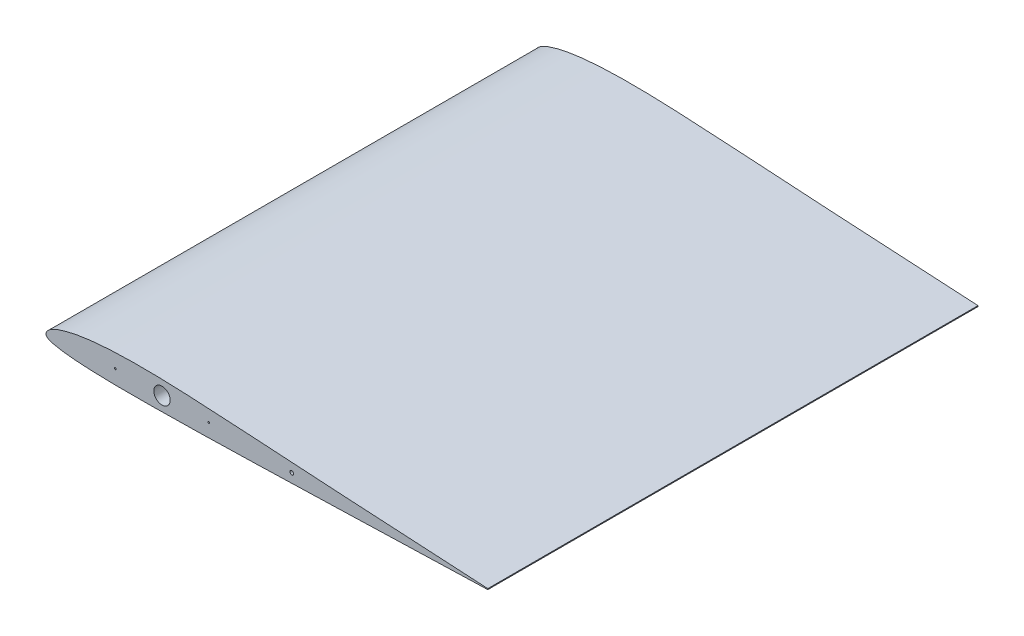
SolidWorks part; units mm, degrees
material "Polyurethane Foam Flexible"
ref_plane "Front Plane" through (0, 0, 0) normal (0, 0, 1) x (1, 0, 0)
ref_plane "Top Plane" through (0, 0, 0) normal (0, 1, 0) x (1, 0, 0)
ref_plane "Right Plane" through (0, 0, 0) normal (1, 0, 0) x (0, 0, -1)
curve "ht32-8-imported"
  spline degree 3 poles (203.2026, 0.2115, 0) (202.75, 0.2358, 0) (201.4822, 0.3036, 0) (199.2299, 0.4276, 0) (196.3046, 0.5865, 0) (192.9787, 0.7694, 0) (189.375, 0.9706, 0) (185.6129, 1.1785, 0) (181.7737, 1.3957, 0) (177.8996, 1.6147, 0) (174.01, 1.8354, 0) (170.1132, 2.0552, 0) (166.2133, 2.2775, 0) (162.3117, 2.4986, 0) (158.4107, 2.722, 0) (154.5106, 2.9441, 0) (150.6142, 3.1678, 0) (146.7204, 3.3936, 0) (142.8309, 3.617, 0) (138.944, 3.8454, 0) (135.0595, 4.0721, 0) (131.1775, 4.3012, 0) (127.2967, 4.5315, 0) (123.4189, 4.7649, 0) (119.5421, 5.0008, 0) (115.6675, 5.2398, 0) (111.7949, 5.4816, 0) (107.9236, 5.7247, 0) (104.0572, 5.9681, 0) (100.1894, 6.212, 0) (96.3188, 6.4543, 0) (92.4477, 6.6946, 0) (88.584, 6.9322, 0) (84.7415, 7.1637, 0) (80.9229, 7.3889, 0) (77.3978, 7.5906, 0) (74.5229, 7.7493, 0) (71.9946, 7.8843, 0) (69.1241, 8.0324, 0) (65.5083, 8.2076, 0) (61.4852, 8.3831, 0) (57.5218, 8.5328, 0) (53.6734, 8.652, 0) (49.9058, 8.739, 0) (46.181, 8.7912, 0) (42.491, 8.8047, 0) (38.8468, 8.7742, 0) (35.2596, 8.6962, 0) (31.7561, 8.5671, 0) (28.3661, 8.3856, 0) (25.1292, 8.152, 0) (22.0798, 7.8688, 0) (19.2587, 7.5428, 0) (16.7019, 7.1837, 0) (14.4336, 6.8058, 0) (12.4541, 6.4216, 0) (10.7471, 6.0418, 0) (9.283, 5.6741, 0) (8.0264, 5.3216, 0) (6.9394, 4.9844, 0) (5.9876, 4.6599, 0) (5.1429, 4.3427, 0) (4.3754, 4.0301, 0) (3.6577, 3.7081, 0) (2.9646, 3.3607, 0) (2.2868, 2.9708, 0) (1.6384, 2.5305, 0) (1.05, 2.0355, 0) (0.5511, 1.4823, 0) (0.1821, 0.8795, 0) (0.0202, 0.3651, 0) (-0.0065, -0.0193, 0) (0.0194, -0.3136, 0) (0.1268, -0.6144, 0) (0.297, -0.8546, 0) (0.4742, -1.036, 0) (0.6922, -1.2054, 0) (0.9846, -1.3848, 0) (1.3525, -1.5668, 0) (1.7794, -1.7448, 0) (2.2605, -1.9172, 0) (2.8067, -2.0876, 0) (3.4413, -2.2602, 0) (4.1881, -2.438, 0) (5.0669, -2.6215, 0) (6.0922, -2.8069, 0) (7.2766, -2.9931, 0) (8.6343, -3.178, 0) (10.1869, -3.3594, 0) (11.9608, -3.5369, 0) (13.9882, -3.7077, 0) (16.2949, -3.8689, 0) (18.8937, -4.0155, 0) (21.7662, -4.1437, 0) (24.8729, -4.2492, 0) (28.1584, -4.3297, 0) (31.5775, -4.3867, 0) (35.0914, -4.4207, 0) (38.6791, -4.4351, 0) (42.3216, -4.4311, 0) (46.0126, -4.4125, 0) (49.7579, -4.3795, 0) (53.5805, -4.3372, 0) (57.5149, -4.2842, 0) (61.5959, -4.2202, 0) (65.8841, -4.1445, 0) (69.584, -4.0721, 0) (72.8088, -4.005, 0) (75.5799, -3.9448, 0) (78.7708, -3.8727, 0) (82.2137, -3.7909, 0) (85.8123, -3.7021, 0) (89.4548, -3.6091, 0) (93.1502, -3.5116, 0) (96.8889, -3.4111, 0) (100.657, -3.3069, 0) (104.4397, -3.2018, 0) (108.2248, -3.0945, 0) (112.0082, -2.9863, 0) (115.791, -2.8766, 0) (119.5782, -2.7658, 0) (123.3765, -2.6523, 0) (127.1945, -2.5376, 0) (131.0416, -2.42, 0) (134.9198, -2.302, 0) (138.8194, -2.1823, 0) (142.7263, -2.0602, 0) (146.6334, -1.9373, 0) (150.5405, -1.8169, 0) (154.4476, -1.6935, 0) (158.3547, -1.5735, 0) (162.2615, -1.4515, 0) (166.1675, -1.3317, 0) (170.0718, -1.2089, 0) (173.9729, -1.0897, 0) (177.8669, -0.9678, 0) (181.7453, -0.8488, 0) (185.5889, -0.7312, 0) (189.3549, -0.6169, 0) (192.9626, -0.5096, 0) (196.292, -0.413, 0) (199.2203, -0.3248, 0) (201.4752, -0.2617, 0) (202.7443, -0.2247, 0) (203.1974, -0.2115, 0) knots 0 0 0 0 0.003316 0.009286 0.0165 0.024744 0.033651 0.0429 0.052304 0.061778 0.071282 0.080801 0.090326 0.099855 0.109385 0.118907 0.128429 0.137932 0.147436 0.156926 0.166412 0.175898 0.185369 0.194848 0.204314 0.213779 0.223243 0.232695 0.242152 0.25158 0.261042 0.270519 0.279949 0.289356 0.298677 0.307928 0.315183 0.319737 0.326448 0.336207 0.346216 0.355902 0.365219 0.374379 0.383467 0.392467 0.401369 0.410123 0.41871 0.427012 0.434953 0.442447 0.449411 0.455723 0.46133 0.466229 0.470471 0.47412 0.47727 0.480016 0.482444 0.484624 0.486615 0.488504 0.490376 0.492284 0.49422 0.496102 0.497896 0.499646 0.501237 0.501776 0.502457 0.503386 0.504071 0.504595 0.505236 0.506086 0.5071 0.508235 0.509467 0.510837 0.512419 0.514277 0.516452 0.518985 0.521897 0.525221 0.529007 0.53333 0.538261 0.543889 0.550243 0.557299 0.56492 0.57298 0.581338 0.589931 0.598683 0.607581 0.616575 0.625681 0.634977 0.644537 0.654462 0.664831 0.675908 0.681531 0.688425 0.696181 0.704877 0.713615 0.722511 0.731528 0.740655 0.749867 0.759101 0.768335 0.777565 0.786786 0.796016 0.805278 0.814581 0.823955 0.833431 0.842961 0.852492 0.862023 0.871554 0.881085 0.890615 0.900146 0.909675 0.9192 0.928718 0.938223 0.947696 0.9571 0.96635 0.975256 0.9835 0.990713 0.996685 1 1 1 1
sketch "Sketch3" plane through (0, 0, 0) normal (0, 0, 1) x (1, 0, 0)
  line L3 (203.2026, 0.2115) -> (203.1974, -0.2115)
  spline S0 degree 3 poles (356.7908, -2985.9067) (413.0686, 1.836) (306.2858, -5.4633) (199.2299, 0.4276) (196.3046, 0.5865) (192.9787, 0.7694) (189.375, 0.9706) (185.6129, 1.1785) (181.7737, 1.3957) (177.8996, 1.6147) (174.01, 1.8354) (170.1132, 2.0552) (166.2133, 2.2775) (162.3117, 2.4986) (158.4107, 2.722) (154.5106, 2.9441) (150.6142, 3.1678) (146.7204, 3.3936) (142.8309, 3.617) (138.944, 3.8454) (135.0595, 4.0721) (131.1775, 4.3012) (127.2967, 4.5315) (123.4189, 4.7649) (119.5421, 5.0008) (115.6675, 5.2398) (111.7949, 5.4816) (107.9236, 5.7247) (104.0572, 5.9681) (100.1894, 6.212) (96.3188, 6.4543) (92.4477, 6.6946) (88.584, 6.9322) (84.7415, 7.1637) (80.9229, 7.3889) (77.3978, 7.5906) (74.5229, 7.7493) (71.9946, 7.8843) (69.1241, 8.0324) (65.5083, 8.2076) (61.4852, 8.3831) (57.5218, 8.5328) (53.6734, 8.652) (49.9058, 8.739) (46.181, 8.7912) (42.491, 8.8047) (38.8468, 8.7742) (35.2596, 8.6962) (31.7561, 8.5671) (28.3661, 8.3856) (25.1292, 8.152) (22.0798, 7.8688) (19.2587, 7.5428) (16.7019, 7.1837) (14.4336, 6.8058) (12.4541, 6.4216) (10.7471, 6.0418) (9.283, 5.6741) (8.0264, 5.3216) (6.9394, 4.9844) (5.9876, 4.6599) (5.1429, 4.3427) (4.3754, 4.0301) (3.6577, 3.7081) (2.9646, 3.3607) (2.2868, 2.9708) (1.6384, 2.5305) (1.05, 2.0355) (0.5511, 1.4823) (0.1821, 0.8795) (0.0202, 0.3651) (-0.0065, -0.0193) (0.0194, -0.3136) (0.1268, -0.6144) (0.297, -0.8546) (0.4742, -1.036) (0.6922, -1.2054) (0.9846, -1.3848) (1.3525, -1.5668) (1.7794, -1.7448) (2.2605, -1.9172) (2.8067, -2.0876) (3.4413, -2.2602) (4.1881, -2.438) (5.0669, -2.6215) (6.0922, -2.8069) (7.2766, -2.9931) (8.6343, -3.178) (10.1869, -3.3594) (11.9608, -3.5369) (13.9882, -3.7077) (16.2949, -3.8689) (18.8937, -4.0155) (21.7662, -4.1437) (24.8729, -4.2492) (28.1584, -4.3297) (31.5775, -4.3867) (35.0914, -4.4207) (38.6791, -4.4351) (42.3216, -4.4311) (46.0126, -4.4125) (49.7579, -4.3795) (53.5805, -4.3372) (57.5149, -4.2842) (61.5959, -4.2202) (65.8841, -4.1445) (69.584, -4.0721) (72.8088, -4.005) (75.5799, -3.9448) (78.7708, -3.8727) (82.2137, -3.7909) (85.8123, -3.7021) (89.4548, -3.6091) (93.1502, -3.5116) (96.8889, -3.4111) (100.657, -3.3069) (104.4397, -3.2018) (108.2248, -3.0945) (112.0082, -2.9863) (115.791, -2.8766) (119.5782, -2.7658) (123.3765, -2.6523) (127.1945, -2.5376) (131.0416, -2.42) (134.9198, -2.302) (138.8194, -2.1823) (142.7263, -2.0602) (146.6334, -1.9373) (150.5405, -1.8169) (154.4476, -1.6935) (158.3547, -1.5735) (162.2615, -1.4515) (166.1675, -1.3317) (170.0718, -1.2089) (173.9729, -1.0897) (177.8669, -0.9678) (181.7453, -0.8488) (185.5889, -0.7312) (189.3549, -0.6169) (192.9626, -0.5096) (196.292, -0.413) (199.2203, -0.3248) (315.412, 2.9269) (430.2694, 18.2159) (630.7155, -2957.7378) knots -0.767748 -0.767748 -0.767748 -0.767748 0.003316 0.009286 0.0165 0.024744 0.033651 0.0429 0.052304 0.061778 0.071282 0.080801 0.090326 0.099855 0.109385 0.118907 0.128429 0.137932 0.147436 0.156926 0.166412 0.175898 0.185369 0.194848 0.204314 0.213779 0.223243 0.232695 0.242152 0.25158 0.261042 0.270519 0.279949 0.289356 0.298677 0.307928 0.315183 0.319737 0.326448 0.336207 0.346216 0.355902 0.365219 0.374379 0.383467 0.392467 0.401369 0.410123 0.41871 0.427012 0.434953 0.442447 0.449411 0.455723 0.46133 0.466229 0.470471 0.47412 0.47727 0.480016 0.482444 0.484624 0.486615 0.488504 0.490376 0.492284 0.49422 0.496102 0.497896 0.499646 0.501237 0.501776 0.502457 0.503386 0.504071 0.504595 0.505236 0.506086 0.5071 0.508235 0.509467 0.510837 0.512419 0.514277 0.516452 0.518985 0.521897 0.525221 0.529007 0.53333 0.538261 0.543889 0.550243 0.557299 0.56492 0.57298 0.581338 0.589931 0.598683 0.607581 0.616575 0.625681 0.634977 0.644537 0.654462 0.664831 0.675908 0.681531 0.688425 0.696181 0.704877 0.713615 0.722511 0.731528 0.740655 0.749867 0.759101 0.768335 0.777565 0.786786 0.796016 0.805278 0.814581 0.823955 0.833431 0.842961 0.852492 0.862023 0.871554 0.881085 0.890615 0.900146 0.909675 0.9192 0.928718 0.938223 0.947696 0.9571 0.96635 0.975256 0.9835 0.990713 0.996685 1.83372 1.83372 1.83372 1.83372 only from (203.2026, 0.2115) to (203.1974, -0.2115) construction
  spline S1 degree 3 poles (203.2026, 0.2115) (202.75, 0.2358) (201.4822, 0.3036) (199.2299, 0.4276) (196.3046, 0.5865) (192.9787, 0.7694) (189.375, 0.9706) (185.6129, 1.1785) (181.7737, 1.3957) (177.8996, 1.6147) (174.01, 1.8354) (170.1132, 2.0552) (166.2133, 2.2775) (162.3117, 2.4986) (158.4107, 2.722) (154.5106, 2.9441) (150.6142, 3.1678) (146.7204, 3.3936) (142.8309, 3.617) (138.944, 3.8454) (135.0595, 4.0721) (131.1775, 4.3012) (127.2967, 4.5315) (123.4189, 4.7649) (119.5421, 5.0008) (115.6675, 5.2398) (111.7949, 5.4816) (107.9236, 5.7247) (104.0572, 5.9681) (100.1894, 6.212) (96.3188, 6.4543) (92.4477, 6.6946) (88.584, 6.9322) (84.7415, 7.1637) (80.9229, 7.3889) (77.3978, 7.5906) (74.5229, 7.7493) (71.9946, 7.8843) (69.1241, 8.0324) (65.5083, 8.2076) (61.4852, 8.3831) (57.5218, 8.5328) (53.6734, 8.652) (49.9058, 8.739) (46.181, 8.7912) (42.491, 8.8047) (38.8468, 8.7742) (35.2596, 8.6962) (31.7561, 8.5671) (28.3661, 8.3856) (25.1292, 8.152) (22.0798, 7.8688) (19.2587, 7.5428) (16.7019, 7.1837) (14.4336, 6.8058) (12.4541, 6.4216) (10.7471, 6.0418) (9.283, 5.6741) (8.0264, 5.3216) (6.9394, 4.9844) (5.9876, 4.6599) (5.1429, 4.3427) (4.3754, 4.0301) (3.6577, 3.7081) (2.9646, 3.3607) (2.2868, 2.9708) (1.6384, 2.5305) (1.05, 2.0355) (0.5511, 1.4823) (0.1821, 0.8795) (0.0202, 0.3651) (-0.0065, -0.0193) (0.0194, -0.3136) (0.1268, -0.6144) (0.297, -0.8546) (0.4742, -1.036) (0.6922, -1.2054) (0.9846, -1.3848) (1.3525, -1.5668) (1.7794, -1.7448) (2.2605, -1.9172) (2.8067, -2.0876) (3.4413, -2.2602) (4.1881, -2.438) (5.0669, -2.6215) (6.0922, -2.8069) (7.2766, -2.9931) (8.6343, -3.178) (10.1869, -3.3594) (11.9608, -3.5369) (13.9882, -3.7077) (16.2949, -3.8689) (18.8937, -4.0155) (21.7662, -4.1437) (24.8729, -4.2492) (28.1584, -4.3297) (31.5775, -4.3867) (35.0914, -4.4207) (38.6791, -4.4351) (42.3216, -4.4311) (46.0126, -4.4125) (49.7579, -4.3795) (53.5805, -4.3372) (57.5149, -4.2842) (61.5959, -4.2202) (65.8841, -4.1445) (69.584, -4.0721) (72.8088, -4.005) (75.5799, -3.9448) (78.7708, -3.8727) (82.2137, -3.7909) (85.8123, -3.7021) (89.4548, -3.6091) (93.1502, -3.5116) (96.8889, -3.4111) (100.657, -3.3069) (104.4397, -3.2018) (108.2248, -3.0945) (112.0082, -2.9863) (115.791, -2.8766) (119.5782, -2.7658) (123.3765, -2.6523) (127.1945, -2.5376) (131.0416, -2.42) (134.9198, -2.302) (138.8194, -2.1823) (142.7263, -2.0602) (146.6334, -1.9373) (150.5405, -1.8169) (154.4476, -1.6935) (158.3547, -1.5735) (162.2615, -1.4515) (166.1675, -1.3317) (170.0718, -1.2089) (173.9729, -1.0897) (177.8669, -0.9678) (181.7453, -0.8488) (185.5889, -0.7312) (189.3549, -0.6169) (192.9626, -0.5096) (196.292, -0.413) (199.2203, -0.3248) (201.4752, -0.2617) (202.7443, -0.2247) (203.1974, -0.2115) knots 0 0 0 0 0.003316 0.009286 0.0165 0.024744 0.033651 0.0429 0.052304 0.061778 0.071282 0.080801 0.090326 0.099855 0.109385 0.118907 0.128429 0.137932 0.147436 0.156926 0.166412 0.175898 0.185369 0.194848 0.204314 0.213779 0.223243 0.232695 0.242152 0.25158 0.261042 0.270519 0.279949 0.289356 0.298677 0.307928 0.315183 0.319737 0.326448 0.336207 0.346216 0.355902 0.365219 0.374379 0.383467 0.392467 0.401369 0.410123 0.41871 0.427012 0.434953 0.442447 0.449411 0.455723 0.46133 0.466229 0.470471 0.47412 0.47727 0.480016 0.482444 0.484624 0.486615 0.488504 0.490376 0.492284 0.49422 0.496102 0.497896 0.499646 0.501237 0.501776 0.502457 0.503386 0.504071 0.504595 0.505236 0.506086 0.5071 0.508235 0.509467 0.510837 0.512419 0.514277 0.516452 0.518985 0.521897 0.525221 0.529007 0.53333 0.538261 0.543889 0.550243 0.557299 0.56492 0.57298 0.581338 0.589931 0.598683 0.607581 0.616575 0.625681 0.634977 0.644537 0.654462 0.664831 0.675908 0.681531 0.688425 0.696181 0.704877 0.713615 0.722511 0.731528 0.740655 0.749867 0.759101 0.768335 0.777565 0.786786 0.796016 0.805278 0.814581 0.823955 0.833431 0.842961 0.852492 0.862023 0.871554 0.881085 0.890615 0.900146 0.909675 0.9192 0.928718 0.938223 0.947696 0.9571 0.96635 0.975256 0.9835 0.990713 0.996685 1 1 1 1
extrude "Airfoil" add sketch "Sketch3" along normal blind 225.425
sketch "Sketch8" plane through (0, 0, 0) normal (0, 0, -1) x (-1, 0, 0)
  line L0 (0, 16.6795) -> (0, -1.637) construction
  line L2 (-53.34, 2.1587) -> (-53.34, 8.6559) construction
  line L3 (-53.34, 2.1587) -> (-53.34, -4.3386) construction
  circle A0 centre (-53.34, 2.1587) radius 3.7592
  spline S2 degree 3 poles (-203.2026, 0.2115) (-202.75, 0.2358) (-201.4822, 0.3036) (-199.2299, 0.4276) (-196.3046, 0.5865) (-192.9787, 0.7694) (-189.375, 0.9706) (-185.6129, 1.1785) (-181.7737, 1.3957) (-177.8996, 1.6147) (-174.01, 1.8354) (-170.1132, 2.0552) (-166.2133, 2.2775) (-162.3117, 2.4986) (-158.4107, 2.722) (-154.5106, 2.9441) (-150.6142, 3.1678) (-146.7204, 3.3936) (-142.8309, 3.617) (-138.944, 3.8454) (-135.0595, 4.0721) (-131.1775, 4.3012) (-127.2967, 4.5315) (-123.4189, 4.7649) (-119.5421, 5.0008) (-115.6675, 5.2398) (-111.7949, 5.4816) (-107.9236, 5.7247) (-104.0572, 5.9681) (-100.1894, 6.212) (-96.3188, 6.4543) (-92.4477, 6.6946) (-88.584, 6.9322) (-84.7415, 7.1637) (-80.9229, 7.3889) (-77.3978, 7.5906) (-74.5229, 7.7493) (-71.9946, 7.8843) (-69.1241, 8.0324) (-65.5083, 8.2076) (-61.4852, 8.3831) (-57.5218, 8.5328) (-53.6734, 8.652) (-49.9058, 8.739) (-46.181, 8.7912) (-42.491, 8.8047) (-38.8468, 8.7742) (-35.2596, 8.6962) (-31.7561, 8.5671) (-28.3661, 8.3856) (-25.1292, 8.152) (-22.0798, 7.8688) (-19.2587, 7.5428) (-16.7019, 7.1837) (-14.4336, 6.8058) (-12.4541, 6.4216) (-10.7471, 6.0418) (-9.283, 5.6741) (-8.0264, 5.3216) (-6.9394, 4.9844) (-5.9876, 4.6599) (-5.1429, 4.3427) (-4.3754, 4.0301) (-3.6577, 3.7081) (-2.9646, 3.3607) (-2.2868, 2.9708) (-1.6384, 2.5305) (-1.05, 2.0355) (-0.5511, 1.4823) (-0.1821, 0.8795) (-0.0202, 0.3651) (0.0065, -0.0193) (-0.0194, -0.3136) (-0.1268, -0.6144) (-0.297, -0.8546) (-0.4742, -1.036) (-0.6922, -1.2054) (-0.9846, -1.3848) (-1.3525, -1.5668) (-1.7794, -1.7448) (-2.2605, -1.9172) (-2.8067, -2.0876) (-3.4413, -2.2602) (-4.1881, -2.438) (-5.0669, -2.6215) (-6.0922, -2.8069) (-7.2766, -2.9931) (-8.6343, -3.178) (-10.1869, -3.3594) (-11.9608, -3.5369) (-13.9882, -3.7077) (-16.2949, -3.8689) (-18.8937, -4.0155) (-21.7662, -4.1437) (-24.8729, -4.2492) (-28.1584, -4.3297) (-31.5775, -4.3867) (-35.0914, -4.4207) (-38.6791, -4.4351) (-42.3216, -4.4311) (-46.0126, -4.4125) (-49.7579, -4.3795) (-53.5805, -4.3372) (-57.5149, -4.2842) (-61.5959, -4.2202) (-65.8841, -4.1445) (-69.584, -4.0721) (-72.8088, -4.005) (-75.5799, -3.9448) (-78.7708, -3.8727) (-82.2137, -3.7909) (-85.8123, -3.7021) (-89.4548, -3.6091) (-93.1502, -3.5116) (-96.8889, -3.4111) (-100.657, -3.3069) (-104.4397, -3.2018) (-108.2248, -3.0945) (-112.0082, -2.9863) (-115.791, -2.8766) (-119.5782, -2.7658) (-123.3765, -2.6523) (-127.1945, -2.5376) (-131.0416, -2.42) (-134.9198, -2.302) (-138.8194, -2.1823) (-142.7263, -2.0602) (-146.6334, -1.9373) (-150.5405, -1.8169) (-154.4476, -1.6935) (-158.3547, -1.5735) (-162.2615, -1.4515) (-166.1675, -1.3317) (-170.0718, -1.2089) (-173.9729, -1.0897) (-177.8669, -0.9678) (-181.7453, -0.8488) (-185.5889, -0.7312) (-189.3549, -0.6169) (-192.9626, -0.5096) (-196.292, -0.413) (-199.2203, -0.3248) (-201.4752, -0.2617) (-202.7443, -0.2247) (-203.1974, -0.2115) knots 0 0 0 0 0.003316 0.009286 0.0165 0.024744 0.033651 0.0429 0.052304 0.061778 0.071282 0.080801 0.090326 0.099855 0.109385 0.118907 0.128429 0.137932 0.147436 0.156926 0.166412 0.175898 0.185369 0.194848 0.204314 0.213779 0.223243 0.232695 0.242152 0.25158 0.261042 0.270519 0.279949 0.289356 0.298677 0.307928 0.315183 0.319737 0.326448 0.336207 0.346216 0.355902 0.365219 0.374379 0.383467 0.392467 0.401369 0.410123 0.41871 0.427012 0.434953 0.442447 0.449411 0.455723 0.46133 0.466229 0.470471 0.47412 0.47727 0.480016 0.482444 0.484624 0.486615 0.488504 0.490376 0.492284 0.49422 0.496102 0.497896 0.499646 0.501237 0.501776 0.502457 0.503386 0.504071 0.504595 0.505236 0.506086 0.5071 0.508235 0.509467 0.510837 0.512419 0.514277 0.516452 0.518985 0.521897 0.525221 0.529007 0.53333 0.538261 0.543889 0.550243 0.557299 0.56492 0.57298 0.581338 0.589931 0.598683 0.607581 0.616575 0.625681 0.634977 0.644537 0.654462 0.664831 0.675908 0.681531 0.688425 0.696181 0.704877 0.713615 0.722511 0.731528 0.740655 0.749867 0.759101 0.768335 0.777565 0.786786 0.796016 0.805278 0.814581 0.823955 0.833431 0.842961 0.852492 0.862023 0.871554 0.881085 0.890615 0.900146 0.909675 0.9192 0.928718 0.938223 0.947696 0.9571 0.96635 0.975256 0.9835 0.990713 0.996685 1 1 1 1 construction
  dimension "D1" = 7.5184
  dimension "D2" = 53.34
extrude "Camera Channel" cut sketch "Sketch8" against normal up to next
sketch "Sketch9" plane through (0, 0, 0) normal (0, 0, -1) x (-1, 0, 0)
  line L0 (-113.03, 2.0876) -> (-113.03, 5.4046) construction
  line L1 (-113.03, 0.3604) -> (-113.03, -2.9566) construction
  circle A0 centre (-113.03, 1.224) radius 0.8636
  circle A1 centre (-53.34, 2.1587) radius 3.7592 construction
  spline S0 degree 3 poles (-370.7177, -1986.1352) (-386.1593, 0.2045) (-292.9152, -4.7275) (-199.2299, 0.4276) (-196.3046, 0.5865) (-192.9787, 0.7694) (-189.375, 0.9706) (-185.6129, 1.1785) (-181.7737, 1.3957) (-177.8996, 1.6147) (-174.01, 1.8354) (-170.1132, 2.0552) (-166.2133, 2.2775) (-162.3117, 2.4986) (-158.4107, 2.722) (-154.5106, 2.9441) (-150.6142, 3.1678) (-146.7204, 3.3936) (-142.8309, 3.617) (-138.944, 3.8454) (-135.0595, 4.0721) (-131.1775, 4.3012) (-127.2967, 4.5315) (-123.4189, 4.7649) (-119.5421, 5.0008) (-115.6675, 5.2398) (-111.7949, 5.4816) (-107.9236, 5.7247) (-104.0572, 5.9681) (-100.1894, 6.212) (-96.3188, 6.4543) (-92.4477, 6.6946) (-88.584, 6.9322) (-84.7415, 7.1637) (-80.9229, 7.3889) (-77.3978, 7.5906) (-74.5229, 7.7493) (-71.9946, 7.8843) (-69.1241, 8.0324) (-65.5083, 8.2076) (-61.4852, 8.3831) (-57.5218, 8.5328) (-53.6734, 8.652) (-49.9058, 8.739) (-46.181, 8.7912) (-42.491, 8.8047) (-38.8468, 8.7742) (-35.2596, 8.6962) (-31.7561, 8.5671) (-28.3661, 8.3856) (-25.1292, 8.152) (-22.0798, 7.8688) (-19.2587, 7.5428) (-16.7019, 7.1837) (-14.4336, 6.8058) (-12.4541, 6.4216) (-10.7471, 6.0418) (-9.283, 5.6741) (-8.0264, 5.3216) (-6.9394, 4.9844) (-5.9876, 4.6599) (-5.1429, 4.3427) (-4.3754, 4.0301) (-3.6577, 3.7081) (-2.9646, 3.3607) (-2.2868, 2.9708) (-1.6384, 2.5305) (-1.05, 2.0355) (-0.5511, 1.4823) (-0.1821, 0.8795) (-0.0202, 0.3651) (0.0065, -0.0193) (-0.0194, -0.3136) (-0.1268, -0.6144) (-0.297, -0.8546) (-0.4742, -1.036) (-0.6922, -1.2054) (-0.9846, -1.3848) (-1.3525, -1.5668) (-1.7794, -1.7448) (-2.2605, -1.9172) (-2.8067, -2.0876) (-3.4413, -2.2602) (-4.1881, -2.438) (-5.0669, -2.6215) (-6.0922, -2.8069) (-7.2766, -2.9931) (-8.6343, -3.178) (-10.1869, -3.3594) (-11.9608, -3.5369) (-13.9882, -3.7077) (-16.2949, -3.8689) (-18.8937, -4.0155) (-21.7662, -4.1437) (-24.8729, -4.2492) (-28.1584, -4.3297) (-31.5775, -4.3867) (-35.0914, -4.4207) (-38.6791, -4.4351) (-42.3216, -4.4311) (-46.0126, -4.4125) (-49.7579, -4.3795) (-53.5805, -4.3372) (-57.5149, -4.2842) (-61.5959, -4.2202) (-65.8841, -4.1445) (-69.584, -4.0721) (-72.8088, -4.005) (-75.5799, -3.9448) (-78.7708, -3.8727) (-82.2137, -3.7909) (-85.8123, -3.7021) (-89.4548, -3.6091) (-93.1502, -3.5116) (-96.8889, -3.4111) (-100.657, -3.3069) (-104.4397, -3.2018) (-108.2248, -3.0945) (-112.0082, -2.9863) (-115.791, -2.8766) (-119.5782, -2.7658) (-123.3765, -2.6523) (-127.1945, -2.5376) (-131.0416, -2.42) (-134.9198, -2.302) (-138.8194, -2.1823) (-142.7263, -2.0602) (-146.6334, -1.9373) (-150.5405, -1.8169) (-154.4476, -1.6935) (-158.3547, -1.5735) (-162.2615, -1.4515) (-166.1675, -1.3317) (-170.0718, -1.2089) (-173.9729, -1.0897) (-177.8669, -0.9678) (-181.7453, -0.8488) (-185.5889, -0.7312) (-189.3549, -0.6169) (-192.9626, -0.5096) (-196.292, -0.413) (-199.2203, -0.3248) (-300.851, 2.5194) (-401.2299, 14.5438) (-558.1905, -1960.49) knots -0.669801 -0.669801 -0.669801 -0.669801 0.003316 0.009286 0.0165 0.024744 0.033651 0.0429 0.052304 0.061778 0.071282 0.080801 0.090326 0.099855 0.109385 0.118907 0.128429 0.137932 0.147436 0.156926 0.166412 0.175898 0.185369 0.194848 0.204314 0.213779 0.223243 0.232695 0.242152 0.25158 0.261042 0.270519 0.279949 0.289356 0.298677 0.307928 0.315183 0.319737 0.326448 0.336207 0.346216 0.355902 0.365219 0.374379 0.383467 0.392467 0.401369 0.410123 0.41871 0.427012 0.434953 0.442447 0.449411 0.455723 0.46133 0.466229 0.470471 0.47412 0.47727 0.480016 0.482444 0.484624 0.486615 0.488504 0.490376 0.492284 0.49422 0.496102 0.497896 0.499646 0.501237 0.501776 0.502457 0.503386 0.504071 0.504595 0.505236 0.506086 0.5071 0.508235 0.509467 0.510837 0.512419 0.514277 0.516452 0.518985 0.521897 0.525221 0.529007 0.53333 0.538261 0.543889 0.550243 0.557299 0.56492 0.57298 0.581338 0.589931 0.598683 0.607581 0.616575 0.625681 0.634977 0.644537 0.654462 0.664831 0.675908 0.681531 0.688425 0.696181 0.704877 0.713615 0.722511 0.731528 0.740655 0.749867 0.759101 0.768335 0.777565 0.786786 0.796016 0.805278 0.814581 0.823955 0.833431 0.842961 0.852492 0.862023 0.871554 0.881085 0.890615 0.900146 0.909675 0.9192 0.928718 0.938223 0.947696 0.9571 0.96635 0.975256 0.9835 0.990713 0.996685 1.727171 1.727171 1.727171 1.727171 only from (-203.2026, 0.2115) to (-203.1974, -0.2115) construction
  spline S1 degree 3 poles (-203.2026, 0.2115) (-202.75, 0.2358) (-201.4822, 0.3036) (-199.2299, 0.4276) (-196.3046, 0.5865) (-192.9787, 0.7694) (-189.375, 0.9706) (-185.6129, 1.1785) (-181.7737, 1.3957) (-177.8996, 1.6147) (-174.01, 1.8354) (-170.1132, 2.0552) (-166.2133, 2.2775) (-162.3117, 2.4986) (-158.4107, 2.722) (-154.5106, 2.9441) (-150.6142, 3.1678) (-146.7204, 3.3936) (-142.8309, 3.617) (-138.944, 3.8454) (-135.0595, 4.0721) (-131.1775, 4.3012) (-127.2967, 4.5315) (-123.4189, 4.7649) (-119.5421, 5.0008) (-115.6675, 5.2398) (-111.7949, 5.4816) (-107.9236, 5.7247) (-104.0572, 5.9681) (-100.1894, 6.212) (-96.3188, 6.4543) (-92.4477, 6.6946) (-88.584, 6.9322) (-84.7415, 7.1637) (-80.9229, 7.3889) (-77.3978, 7.5906) (-74.5229, 7.7493) (-71.9946, 7.8843) (-69.1241, 8.0324) (-65.5083, 8.2076) (-61.4852, 8.3831) (-57.5218, 8.5328) (-53.6734, 8.652) (-49.9058, 8.739) (-46.181, 8.7912) (-42.491, 8.8047) (-38.8468, 8.7742) (-35.2596, 8.6962) (-31.7561, 8.5671) (-28.3661, 8.3856) (-25.1292, 8.152) (-22.0798, 7.8688) (-19.2587, 7.5428) (-16.7019, 7.1837) (-14.4336, 6.8058) (-12.4541, 6.4216) (-10.7471, 6.0418) (-9.283, 5.6741) (-8.0264, 5.3216) (-6.9394, 4.9844) (-5.9876, 4.6599) (-5.1429, 4.3427) (-4.3754, 4.0301) (-3.6577, 3.7081) (-2.9646, 3.3607) (-2.2868, 2.9708) (-1.6384, 2.5305) (-1.05, 2.0355) (-0.5511, 1.4823) (-0.1821, 0.8795) (-0.0202, 0.3651) (0.0065, -0.0193) (-0.0194, -0.3136) (-0.1268, -0.6144) (-0.297, -0.8546) (-0.4742, -1.036) (-0.6922, -1.2054) (-0.9846, -1.3848) (-1.3525, -1.5668) (-1.7794, -1.7448) (-2.2605, -1.9172) (-2.8067, -2.0876) (-3.4413, -2.2602) (-4.1881, -2.438) (-5.0669, -2.6215) (-6.0922, -2.8069) (-7.2766, -2.9931) (-8.6343, -3.178) (-10.1869, -3.3594) (-11.9608, -3.5369) (-13.9882, -3.7077) (-16.2949, -3.8689) (-18.8937, -4.0155) (-21.7662, -4.1437) (-24.8729, -4.2492) (-28.1584, -4.3297) (-31.5775, -4.3867) (-35.0914, -4.4207) (-38.6791, -4.4351) (-42.3216, -4.4311) (-46.0126, -4.4125) (-49.7579, -4.3795) (-53.5805, -4.3372) (-57.5149, -4.2842) (-61.5959, -4.2202) (-65.8841, -4.1445) (-69.584, -4.0721) (-72.8088, -4.005) (-75.5799, -3.9448) (-78.7708, -3.8727) (-82.2137, -3.7909) (-85.8123, -3.7021) (-89.4548, -3.6091) (-93.1502, -3.5116) (-96.8889, -3.4111) (-100.657, -3.3069) (-104.4397, -3.2018) (-108.2248, -3.0945) (-112.0082, -2.9863) (-115.791, -2.8766) (-119.5782, -2.7658) (-123.3765, -2.6523) (-127.1945, -2.5376) (-131.0416, -2.42) (-134.9198, -2.302) (-138.8194, -2.1823) (-142.7263, -2.0602) (-146.6334, -1.9373) (-150.5405, -1.8169) (-154.4476, -1.6935) (-158.3547, -1.5735) (-162.2615, -1.4515) (-166.1675, -1.3317) (-170.0718, -1.2089) (-173.9729, -1.0897) (-177.8669, -0.9678) (-181.7453, -0.8488) (-185.5889, -0.7312) (-189.3549, -0.6169) (-192.9626, -0.5096) (-196.292, -0.413) (-199.2203, -0.3248) (-201.4752, -0.2617) (-202.7443, -0.2247) (-203.1974, -0.2115) knots 0 0 0 0 0.003316 0.009286 0.0165 0.024744 0.033651 0.0429 0.052304 0.061778 0.071282 0.080801 0.090326 0.099855 0.109385 0.118907 0.128429 0.137932 0.147436 0.156926 0.166412 0.175898 0.185369 0.194848 0.204314 0.213779 0.223243 0.232695 0.242152 0.25158 0.261042 0.270519 0.279949 0.289356 0.298677 0.307928 0.315183 0.319737 0.326448 0.336207 0.346216 0.355902 0.365219 0.374379 0.383467 0.392467 0.401369 0.410123 0.41871 0.427012 0.434953 0.442447 0.449411 0.455723 0.46133 0.466229 0.470471 0.47412 0.47727 0.480016 0.482444 0.484624 0.486615 0.488504 0.490376 0.492284 0.49422 0.496102 0.497896 0.499646 0.501237 0.501776 0.502457 0.503386 0.504071 0.504595 0.505236 0.506086 0.5071 0.508235 0.509467 0.510837 0.512419 0.514277 0.516452 0.518985 0.521897 0.525221 0.529007 0.53333 0.538261 0.543889 0.550243 0.557299 0.56492 0.57298 0.581338 0.589931 0.598683 0.607581 0.616575 0.625681 0.634977 0.644537 0.654462 0.664831 0.675908 0.681531 0.688425 0.696181 0.704877 0.713615 0.722511 0.731528 0.740655 0.749867 0.759101 0.768335 0.777565 0.786786 0.796016 0.805278 0.814581 0.823955 0.833431 0.842961 0.852492 0.862023 0.871554 0.881085 0.890615 0.900146 0.909675 0.9192 0.928718 0.938223 0.947696 0.9571 0.96635 0.975256 0.9835 0.990713 0.996685 1 1 1 1 construction
  dimension "D2" = 1.7272
  dimension "D1" = 59.69
extrude "Cut-Extrude1" cut sketch "Sketch9" against normal through all
sketch "Sketch10" plane through (0, 0, 0) normal (0, 0, -1) x (-1, 0, 0)
  line L0 (-74.803, 2.1587) -> (-53.34, 2.1587) construction
  line L1 (-53.34, 2.1587) -> (-31.877, 2.1587) construction
  circle A0 centre (-74.803, 2.1587) radius 0.4064
  circle A1 centre (-31.877, 2.1587) radius 0.4064
  dimension "D1" = 0.8128
  dimension "D2" = 42.926
extrude "Cut-Extrude2" cut sketch "Sketch10" against normal through all
